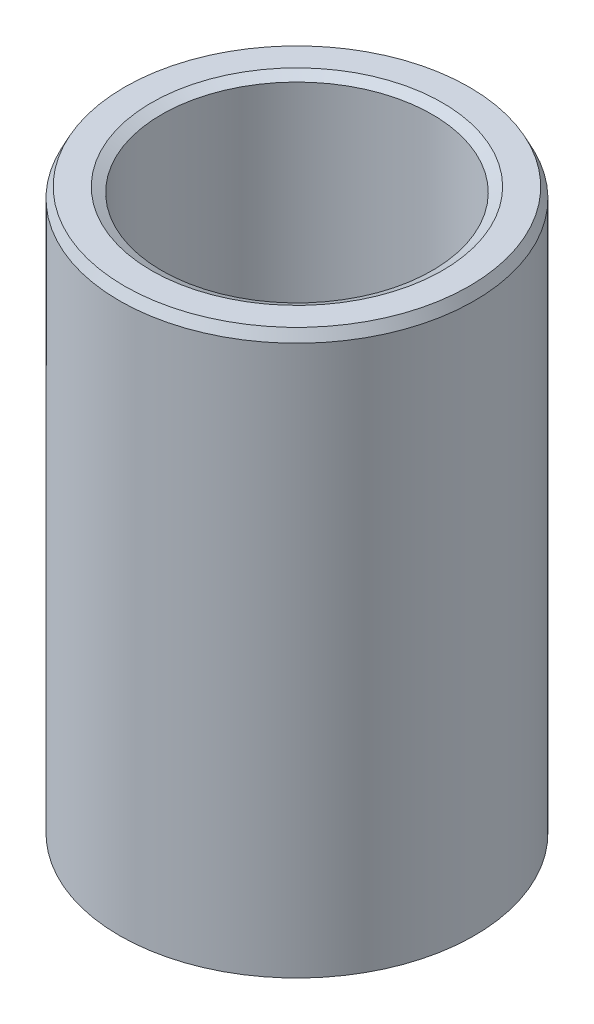
SolidWorks part; units mm, degrees
ref_plane "Front Plane" through (0, 0, 0) normal (0, 0, 1) x (1, 0, 0)
ref_plane "Top Plane" through (0, 0, 0) normal (0, 1, 0) x (1, 0, 0)
ref_plane "Right Plane" through (0, 0, 0) normal (1, 0, 0) x (0, 0, -1)
sketch "Sketch1" plane through (0, 0, 0) normal (0, 1, 0) x (1, 0, 0)
  circle A0 centre (0, 0) radius 25
  dimension "SLEEVE_OD" = 50
extrude "Boss-Extrude1" add sketch "Sketch1" along normal blind 79.5943
sketch "Sketch2" plane through (0, 0, 0) normal (0, 1, 0) x (1, 0, 0)
  circle A0 centre (0, 0) radius 19.0588
  dimension "BORE_D" = 38.1176
extrude "Cut-Extrude1" cut sketch "Sketch2" along normal through all
chamfer "Chamfer1" distance 1.4324 angle 26.551 4 edges at (0, 79.5943, 19.0588) (0, 0, 19.0588) (0, 0, 25) (0, 79.5943, 25) first distance on face at (0, 79.5943, 19.0588) first distance on face at (0, 0, 19.0588) first distance on face at (0, 79.5943, 25)
